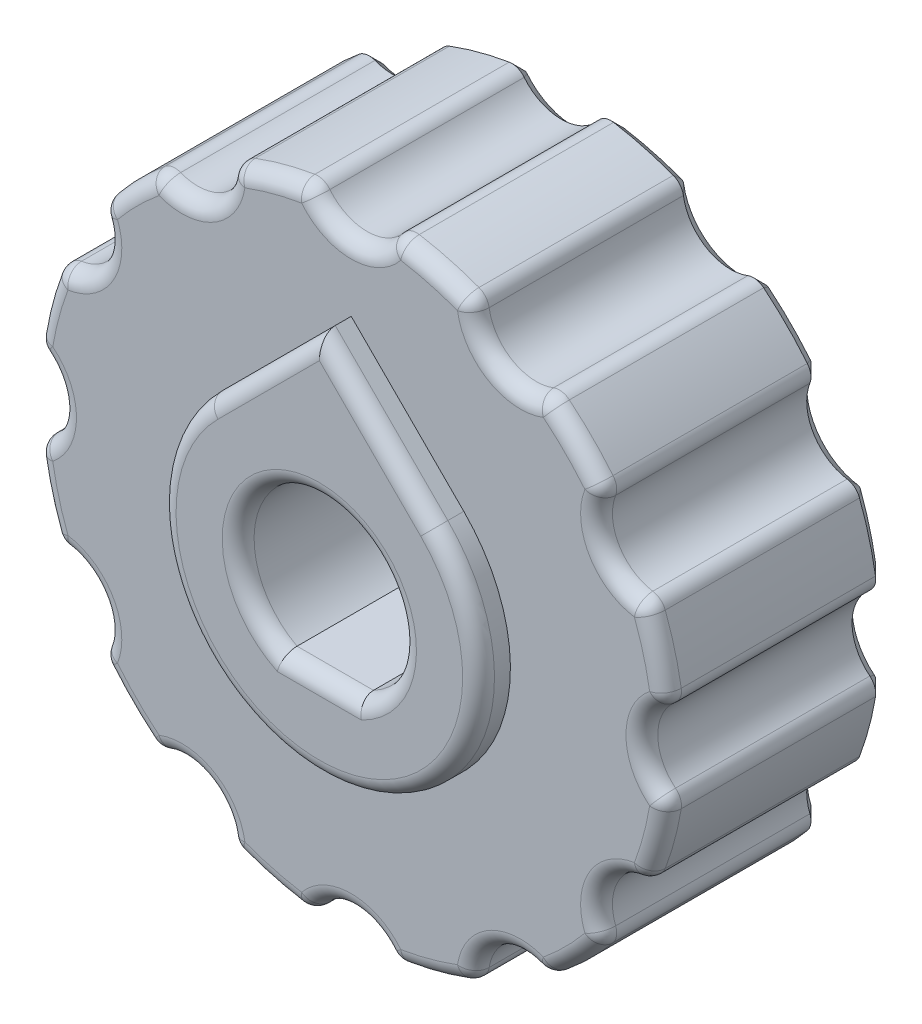
SolidWorks part; units mm, degrees
material "Custom Plastic"
ref_plane "Front Plane" through (0, 0, 0) normal (0, 0, 1) x (1, 0, 0)
ref_plane "Top Plane" through (0, 0, 0) normal (0, 1, 0) x (1, 0, 0)
ref_plane "Right Plane" through (0, 0, 0) normal (1, 0, 0) x (0, 0, -1)
sketch "Sketch1" plane through (0, 0, 0) normal (0, 0, 1) x (1, 0, 0)
  line L0 (1.2, -2.25) -> (-1.2, -2.25)
  circle A0 centre (0, 0) radius 10
  arc A1 (1.2, -2.25) -> (-1.2, -2.25) centre (0, 0) ccw
  dimension "D1" = 2.55
  dimension "D3" = 20
  dimension "D2" = 2.25
extrude "Boss-Extrude1" add sketch "Sketch1" along normal blind 8
sketch "Sketch2" plane through (0, 0, 8) normal (0, 0, 1) x (1, 0, 0)
  circle A0 centre (10.6273, 0) radius 1.5
  dimension "D1" = 3
extrude "Cut-Extrude1" cut sketch "Sketch2" against normal through all
ref_axis "Axis1" through (0, 0, 8) along (0, 0, -1)
fillet "Fillet2" radius 0.5 2 edges at (9.9127, -1.3188, 4) (9.9127, 1.3188, 4)
pattern_circular "CirPattern1" count 12 over 360 about axis through (0, 0, 8) along (0, 0, -1) of "Cut-Extrude1", "Fillet2"
sketch "Sketch3" plane through (0, 0, 8) normal (0, 0, 1) x (1, 0, 0)
  line L0 (0, 7.0711) -> (-3.5355, 3.5355)
  line L1 (0, 7.0711) -> (3.5355, 3.5355)
  arc A0 (-3.5355, 3.5355) -> (3.5355, 3.5355) centre (0, 0) ccw
  circle A1 centre (0, 0) radius 11.3431
  dimension "D1" = 5
extrude "Cut-Extrude2" cut sketch "Sketch3" against normal blind 1
fillet "Fillet1" radius 0.5 53 edges at (-1.7678, 5.3033, 8) (0, -5, 8) (1.7678, 5.3033, 8) (0, 2.55, 8) (0, -2.25, 8) (-7.8313, -6.1135, 7) (-7.9045, -4.5637, 7) (-9.2101, -3.7254, 7) (-9.6593, -2.5882, 7) (-9.8389, -1.3788, 7) (-9.1273, 0, 7) (-9.8389, 1.3788, 7) (-9.6593, 2.5882, 7) (-9.2101, 3.7254, 7) (-7.9045, 4.5637, 7) (-7.8313, 6.1135, 7) (-7.0711, 7.0711, 7) (-6.1135, 7.8313, 7) (-4.5637, 7.9045, 7) (-3.7254, 9.2101, 7) (-2.5882, 9.6593, 7) (-1.3788, 9.8389, 7) (0, 9.1273, 7) (1.3788, 9.8389, 7) (2.5882, 9.6593, 7) (3.7254, 9.2101, 7) (4.5637, 7.9045, 7) (6.1135, 7.8313, 7) (7.0711, 7.0711, 7) (7.8313, 6.1135, 7) (7.9045, 4.5637, 7) (9.2101, 3.7254, 7) (9.6593, 2.5882, 7) (9.8389, 1.3788, 7) (9.1273, 0, 7) (9.8389, -1.3788, 7) (9.6593, -2.5882, 7) (9.2101, -3.7254, 7) (7.9045, -4.5637, 7) (7.8313, -6.1135, 7) (7.0711, -7.0711, 7) (6.1135, -7.8313, 7) (4.5637, -7.9045, 7) (3.7254, -9.2101, 7) (2.5882, -9.6593, 7) (1.3788, -9.8389, 7) (0, -9.1273, 7) (-1.3788, -9.8389, 7) (-2.5882, -9.6593, 7) (-3.7254, -9.2101, 7) (-4.5637, -7.9045, 7) (-6.1135, -7.8313, 7) (-7.0711, -7.0711, 7)
chamfer "Chamfer1" distance 0.4 angle 45 48 edges at (4.5637, 7.9045, 0) (0, 9.1273, 0) (-4.5637, 7.9045, 0) (-7.9045, 4.5637, 0) (-9.1273, 0, 0) (-7.9045, -4.5637, 0) (-4.5637, -7.9045, 0) (0, -9.1273, 0) (4.5637, -7.9045, 0) (7.9045, -4.5637, 0) (9.1273, 0, 0) (7.9045, 4.5637, 0) (7.8313, 6.1135, 0) (7.0711, 7.0711, 0) (6.1135, 7.8313, 0) (3.7254, 9.2101, 0) (2.5882, 9.6593, 0) (1.3788, 9.8389, 0) (-1.3788, 9.8389, 0) (-2.5882, 9.6593, 0) (-3.7254, 9.2101, 0) (-6.1135, 7.8313, 0) (-7.0711, 7.0711, 0) (-7.8313, 6.1135, 0) (-9.2101, 3.7254, 0) (-9.6593, 2.5882, 0) (-9.8389, 1.3788, 0) (-9.8389, -1.3788, 0) (-9.6593, -2.5882, 0) (-9.2101, -3.7254, 0) (-7.8313, -6.1135, 0) (-7.0711, -7.0711, 0) (-6.1135, -7.8313, 0) (-3.7254, -9.2101, 0) (-2.5882, -9.6593, 0) (-1.3788, -9.8389, 0) (1.3788, -9.8389, 0) (2.5882, -9.6593, 0) (3.7254, -9.2101, 0) (6.1135, -7.8313, 0) (7.0711, -7.0711, 0) (7.8313, -6.1135, 0) (9.2101, -3.7254, 0) (9.6593, -2.5882, 0) (9.8389, -1.3788, 0) (9.8389, 1.3788, 0) (9.6593, 2.5882, 0) (9.2101, 3.7254, 0)
chamfer "Chamfer2" distance 0.6 angle 75 2 edges at (0, -2.25, 0) (0, 2.55, 0) first distance on face at (0, 0, 0)
